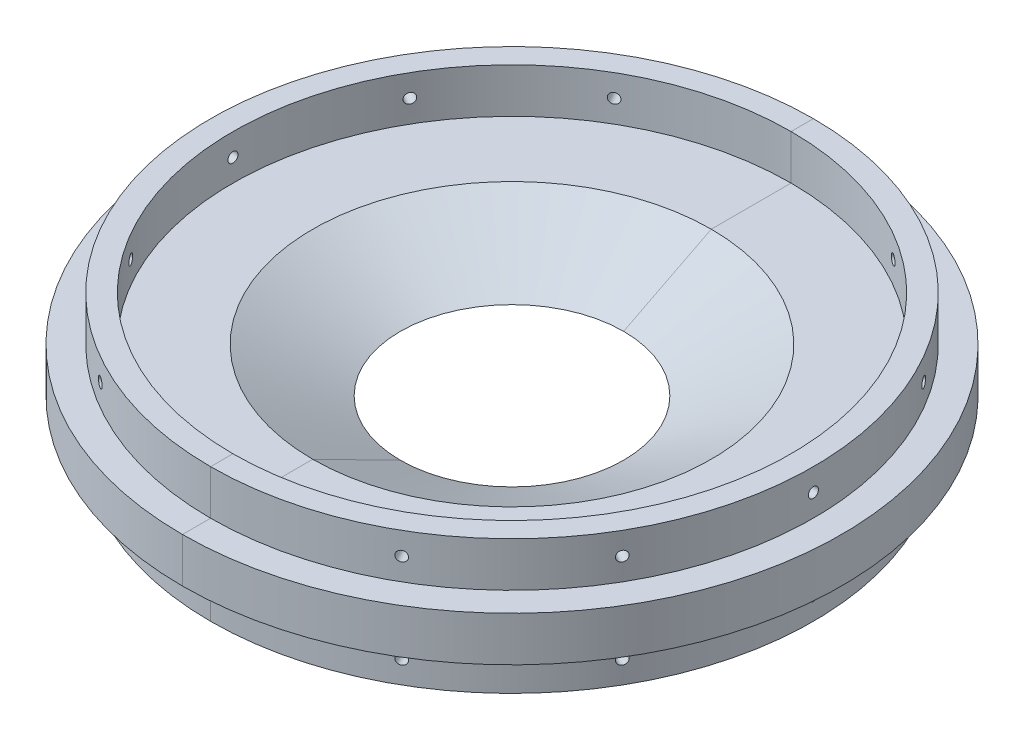
SolidWorks part; units mm, degrees
ref_plane "Front Plane" through (0, 0, 0) normal (0, 0, 1) x (1, 0, 0)
ref_plane "Top Plane" through (0, 0, 0) normal (0, 1, 0) x (1, 0, 0)
ref_plane "Right Plane" through (0, 0, 0) normal (1, 0, 0) x (0, 0, -1)
sketch "Sketch1" plane through (0, 0, 0) normal (0, 1, 0) x (1, 0, 0)
  circle A0 centre (0, 0) radius 93.726
  circle A1 centre (0, 0) radius 31.75
  dimension "D1" = 187.452
  dimension "D2" = 63.5
extrude "Boss-Extrude1" add sketch "Sketch1" along normal mid plane 12.7
sketch "Sketch5" plane through (0, 6.35, 0) normal (0, 1, 0) x (1, 0, 0)
  circle A0 centre (0, 0) radius 85.725
  circle A1 centre (0, 0) radius 79.375
  dimension "D1" = 171.45
  dimension "D2" = 158.75
extrude "Boss-Extrude2" add sketch "Sketch5" along normal blind 12.7
ref_plane "Plane1" through (0, 0, -85.725) normal (0, 0, -1) x (-1, 0, 0)
sketch "Sketch6" plane through (0, 0, -85.725) normal (0, 0, -1) x (-1, 0, 0)
  line L0 (0, 55) -> (0, -55) construction
  line L1 (93.726, 6.35) -> (-93.726, 6.35) construction
  circle A0 centre (0, 12.7) radius 1.4351
  dimension "D1" = 2.8702
  dimension "D2" = 6.35
extrude "Cut-Extrude1" cut sketch "Sketch6" against normal blind 12.7
pattern_circular "CirPattern1" count 12 over 360 about axis through (0, 6.35, 0) along (0, -1, 0) of "Cut-Extrude1" reverse direction yes
mirror "Mirror1" about plane through (0, 0, 0) normal (0, 1, 0) of "CirPattern1", "Cut-Extrude1", "Boss-Extrude2"
sketch "Sketch7" plane through (0, 19.05, 0) normal (0, 1, 0) x (1, 0, 0)
  line L0 (-25.7878, 75.0692) -> (-28.1663, 80.9657)
  line L1 (28.1663, 80.9657) -> (25.7878, 75.0692)
  arc A0 (28.1663, 80.9657) -> (-28.1663, 80.9657) centre (0, 0) ccw
  circle A1 centre (0, 0) radius 85.725 construction
  arc A2 (25.7878, 75.0692) -> (-25.7878, 75.0692) centre (0, 0) ccw
  circle A3 centre (0, 0) radius 79.375 construction
extrude "Boss-Extrude3" add sketch "Sketch7" against normal up to surface (12.7 mm away) up to face at (0, 6.35, 85.725)
mirror "Mirror3" about plane through (0, 0, 0) normal (0, 1, 0) of "Boss-Extrude3"
mirror "Mirror4" about plane through (0, 0, 0) normal (0, 0, 1) of "Boss-Extrude3"
mirror "Mirror5" about plane through (0, 0, 0) normal (0, 1, 0) of "Mirror4"
sketch "Sketch4" plane through (0, 0, 0) normal (0, 0, 1) x (1, 0, 0)
  line L0 (0, 23.2786) -> (0, -14.9525) construction
sketch "Sketch3" plane through (0, 0, 0) normal (0, 0, 1) x (1, 0, 0)
  line L0 (-31.75, -6.35) -> (-56.6752, 6.35)
  line L1 (93.726, 6.35) -> (-93.726, 6.35) construction
  line L2 (-56.6752, 6.35) -> (-31.75, 6.35)
  line L3 (-31.75, 6.35) -> (-31.75, -6.35)
  line L4 (-31.75, -6.35) -> (31.75, -6.35) construction
  line L6 (31.75, 6.35) -> (-31.75, 6.35) construction
  point P2 (0, 0)
  point P6 (0, 0)
  point P9 (0, 0)
  dimension "D1" = 27
revolve "Cut-Revolve1" cut sketch "Sketch3" angle 360 about L0
split "Split1" trim tools "Right Plane" bodies to split 103 resulting bodies 104 105
